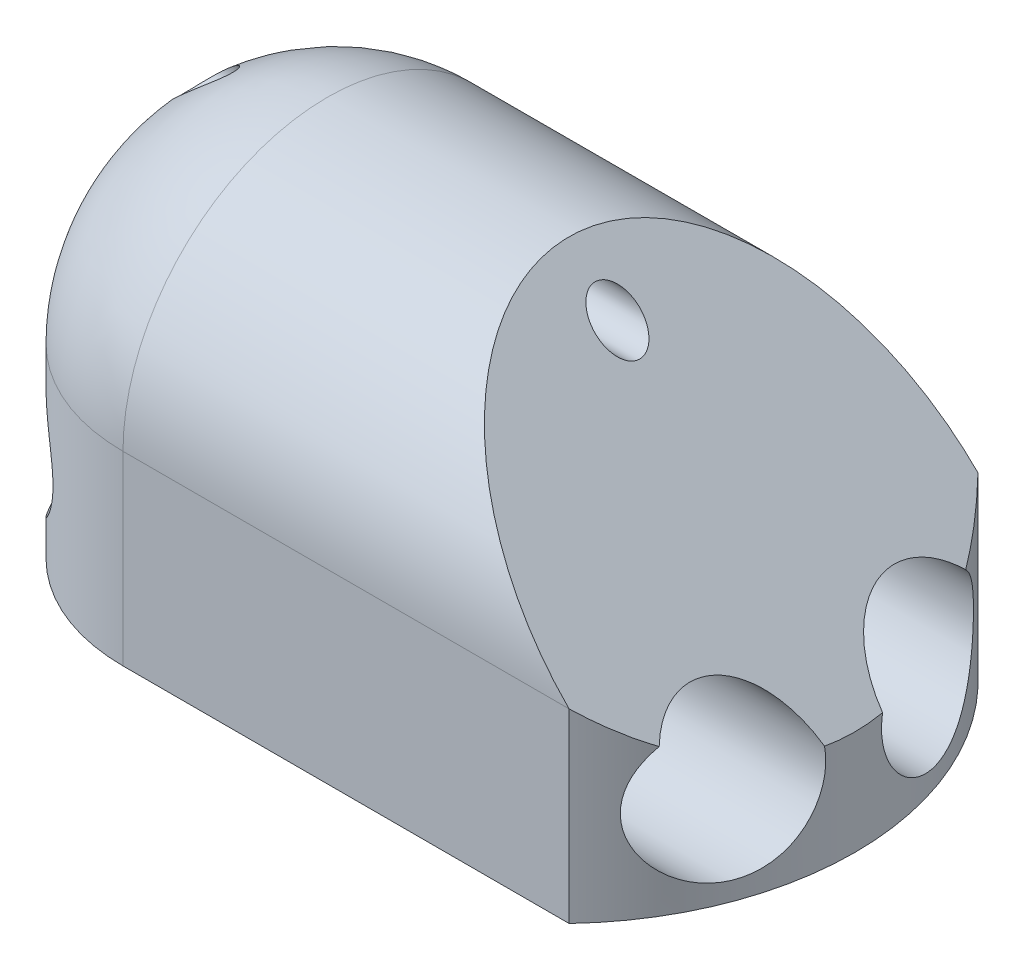
SolidWorks part; units mm, degrees
ref_plane "Front Plane" through (0, 0, 0) normal (0, 0, 1) x (1, 0, 0)
ref_plane "Top Plane" through (0, 0, 0) normal (0, 1, 0) x (1, 0, 0)
ref_plane "Right Plane" through (0, 0, 0) normal (1, 0, 0) x (0, 0, -1)
sketch "Sketch1" plane through (0, 0, 0) normal (0, 1, 0) x (1, 0, 0)
  line L1 (0, 0) -> (-21.59, 0)
  line L2 (0, 0) -> (0, 13.97)
  line L3 (0, 13.97) -> (-21.59, 13.97)
  line L4 (-21.59, 0) -> (-21.59, 13.97)
  dimension "length" = 21.59
  dimension "width" = 13.97
extrude "depth a" add sketch "Sketch1" along normal blind 6.35
sketch "Sketch4" plane through (0, 0, 0) normal (1, 0, 0) x (0, 0, -1)
  line L3 (0, 6.35) -> (13.97, 6.35) construction
  line L4 (0, 6.35) -> (13.97, 6.35)
  arc A0 (0, 6.35) -> (13.97, 6.35) centre (6.985, 6.35) cw
extrude "round extrude" add sketch "Sketch4" against normal up to surface (21.59 mm away) up to face at (-21.59, 3.175, -6.985)
sketch "Sketch5" plane through (0, 0, 0) normal (0, 0, 1) x (1, 0, 0)
  line L0 (0, 6.35) -> (0, 13.335)
  line L1 (0, 13.335) -> (-6.985, 13.335)
  line L2 (0, 13.335) -> (-21.59, 13.335) construction
  line L3 (-6.985, 13.335) -> (0, 6.35)
  line L4 (-10.795, -3.2288) -> (-10.795, 15.9288) construction
  line L9 (-21.59, 6.35) -> (0, 6.35) construction
  point P10 (-10.795, 6.35)
  point P16 (-10.795, 6.35)
  dimension "D1" = 45
extrude "angle cut" cut sketch "Sketch5" against normal through all
sketch "string hole " plane through (0, 0, 0) normal (1, 0, 0) x (0, 0, -1)
  line L0 (6.985, 6.35) -> (6.985, 13.335) construction
  line L1 (13.97, 6.35) -> (0, 6.35) construction
  circle A0 centre (6.985, 11.684) radius 0.762
  arc A1 (13.97, 6.35) -> (0, 6.35) centre (6.985, 6.35) ccw construction
  dimension "D1" = 1.524
  dimension "D2" = 5.334
extrude "string hole cut" cut sketch "string hole " against normal through all
sketch "elastic holes" plane through (0, 0, 0) normal (1, 0, 0) x (0, 0, -1)
  line L1 (13.97, 6.35) -> (0, 6.35) construction
  line L2 (0, 0) -> (13.97, 0) construction
  line L3 (6.985, 0) -> (6.985, 6.35) construction
  line L5 (6.985, 3.175) -> (0, 3.175) construction
  line L7 (0, 6.35) -> (0, 0) construction
  circle A0 centre (3.4925, 3.175) radius 2.54
  circle A1 centre (10.4775, 3.175) radius 2.54
  point P5 (6.985, 6.35)
  point P8 (3.4925, 3.175)
  point P13 (6.985, 3.175)
  point P17 (6.985, 0)
  point P20 (0, 3.175)
  dimension "D1" = 5.08
extrude "elastic hole cut" cut sketch "elastic holes" against normal through all
fillet "Fillet1" radius 6.35 3 edges at (-21.59, 3.175, 0) (-21.59, 3.175, -13.97) (-21.59, 13.335, -6.985)
sketch "guide" plane through (0, 0, 0) normal (0, 1, 0) x (1, 0, 0)
  line L0 (0, 13.97) -> (0, 0)
  arc A1 (0, 13.97) -> (0, 0) centre (-7.378, 6.985) cw
  dimension "D1" = 10.16
extrude "guide outie" add sketch "guide" along normal up to surface (6.35 mm away) up to face at (-4.572, 10.922, -6.985)
sketch "Sketch7" plane through (0, 0, 0) normal (-1, 0, 0) x (0, 0, 1)
  circle A0 centre (-3.4925, 3.175) radius 2.54 construction
  circle A1 centre (-10.4775, 3.175) radius 2.54 construction
  circle A2 centre (-3.4925, 3.175) radius 2.54
  circle A3 centre (-10.4775, 3.175) radius 2.54
extrude "elastic hole cut 2" cut sketch "Sketch7" against normal through all
